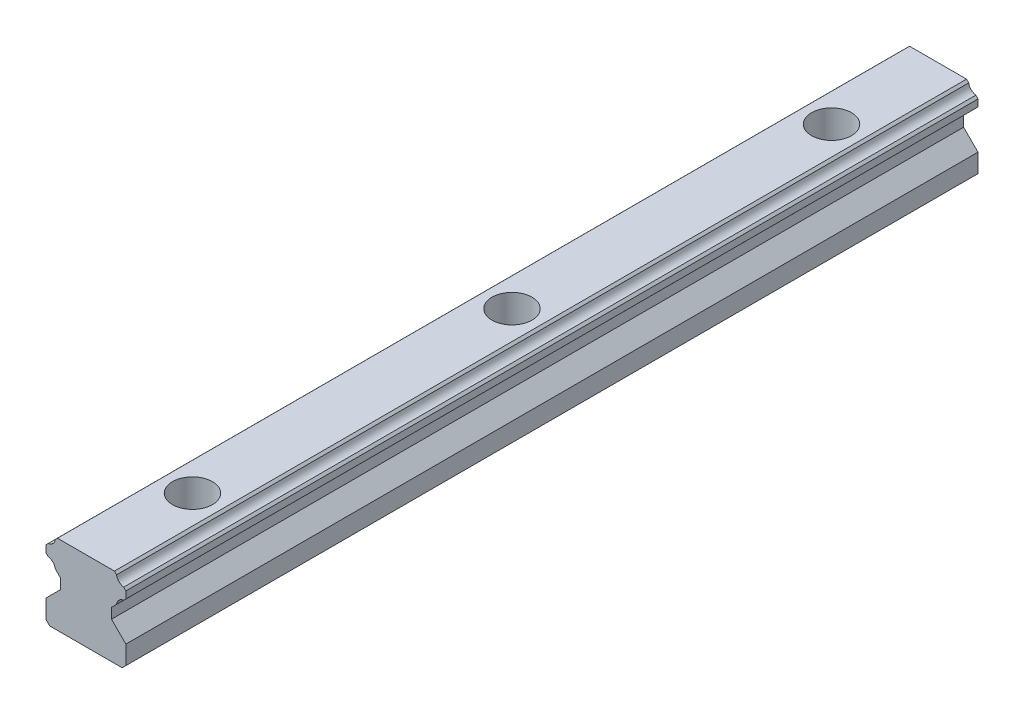
SolidWorks part; units mm, degrees
ref_plane "Front Plane" through (0, 0, 0) normal (0, 0, 1) x (1, 0, 0)
ref_plane "Top Plane" through (0, 0, 0) normal (0, 1, 0) x (1, 0, 0)
ref_plane "Right Plane" through (0, 0, 0) normal (1, 0, 0) x (0, 0, -1)
sketch "Sketch1" plane through (-20, 0, 0) normal (0, 0, 1) x (1, 0, 0)
  line L0 (12.5, 0.7) -> (13.2, 0)
  line L1 (13.2, 0) -> (26.8, 0)
  line L2 (27.5, 4.2) -> (27.5, 0.7)
  line L3 (24.8, 6.9) -> (27.5, 4.2)
  line L4 (24.8, 8.84) -> (24.8, 6.9)
  line L5 (25.7559, 9.7942) -> (24.8, 8.84)
  line L6 (27.5, 11.54) -> (27.0943, 11.1343)
  line L7 (27.5, 12.85) -> (27.5, 11.54)
  line L8 (27.0943, 13.2684) -> (27.5, 12.85)
  line L9 (25.35, 15) -> (25.7559, 14.5941)
  line L10 (27.5, 0.7) -> (26.8, 0)
  line L11 (25.35, 15) -> (14.65, 15)
  line L12 (14.65, 15) -> (14.2441, 14.5941)
  line L13 (12.9057, 13.2684) -> (12.5, 12.85)
  line L14 (12.5, 12.85) -> (12.5, 11.54)
  line L15 (12.5, 11.54) -> (12.9057, 11.1343)
  line L16 (14.2441, 9.7942) -> (15.2, 8.84)
  line L17 (15.2, 8.84) -> (15.2, 6.9)
  line L18 (15.2, 6.9) -> (12.5, 4.2)
  line L19 (12.5, 4.2) -> (12.5, 0.7)
  line L20 (20, 15) -> (20, 0) construction
  arc A0 (27.0943, 11.1343) -> (25.7559, 9.7942) centre (27.3023, 9.5882) ccw
  arc A1 (25.7559, 14.5941) -> (27.0943, 13.2684) centre (27.3003, 14.8148) ccw
  arc A2 (14.2441, 14.5941) -> (12.9057, 13.2684) centre (12.6997, 14.8148) cw
  arc A3 (12.9057, 11.1343) -> (14.2441, 9.7942) centre (12.6977, 9.5882) cw
  dimension "D14" = 1.56
  dimension "D1" = 15
  dimension "D2" = 0.7
  dimension "D3" = 0.7
  dimension "D4" = 4.2
  dimension "D5" = 6.9
  dimension "D6" = 8.84
  dimension "D7" = 4.8
  dimension "D8" = 5.7559
  dimension "D9" = 0.4059
  dimension "D10" = 0.4059
  dimension "D11" = 1.7316
  dimension "D12" = 2.15
  dimension "D13" = 3.46
  dimension "D15" = 7.0943
  dimension "D16" = 3.8657
  dimension "D17" = 5.2058
  dimension "D18" = 15
extrude "Extrude1" add sketch "Sketch1" against normal blind 160
sketch "Sketch2" plane through (0, 0, 0) normal (1, 0, 0) x (0, 0, -1)
  line L0 (20, 15) -> (23.75, 15)
  line L1 (23.75, 15) -> (23.75, 9.7)
  line L2 (23.75, 9.7) -> (22.25, 9.7)
  line L3 (22.25, 9.7) -> (22.25, 0)
  line L4 (22.25, 0) -> (20, 0)
  line L5 (20, 0) -> (20, 15) construction
  line L6 (20, 0) -> (20, 15) construction
  line L7 (20, 15) -> (20, 0)
  line L8 (160, 0) -> (0, 0) construction
  line L9 (160, 15) -> (0, 15) construction
  dimension "D1" = 5.3
  dimension "D2" = 7.5
  dimension "D3" = 4.5
  dimension "D4" = 20
revolve "Cut-Revolve1" cut sketch "Sketch2" angle 360 about L6 reverse direction yes
ref_axis "Axis1" through (0, 0, -168) along (0, 0, 1)
pattern_linear "LPattern1" count 3 spacing 60 along (0, 0, -1) of "Cut-Revolve1"
